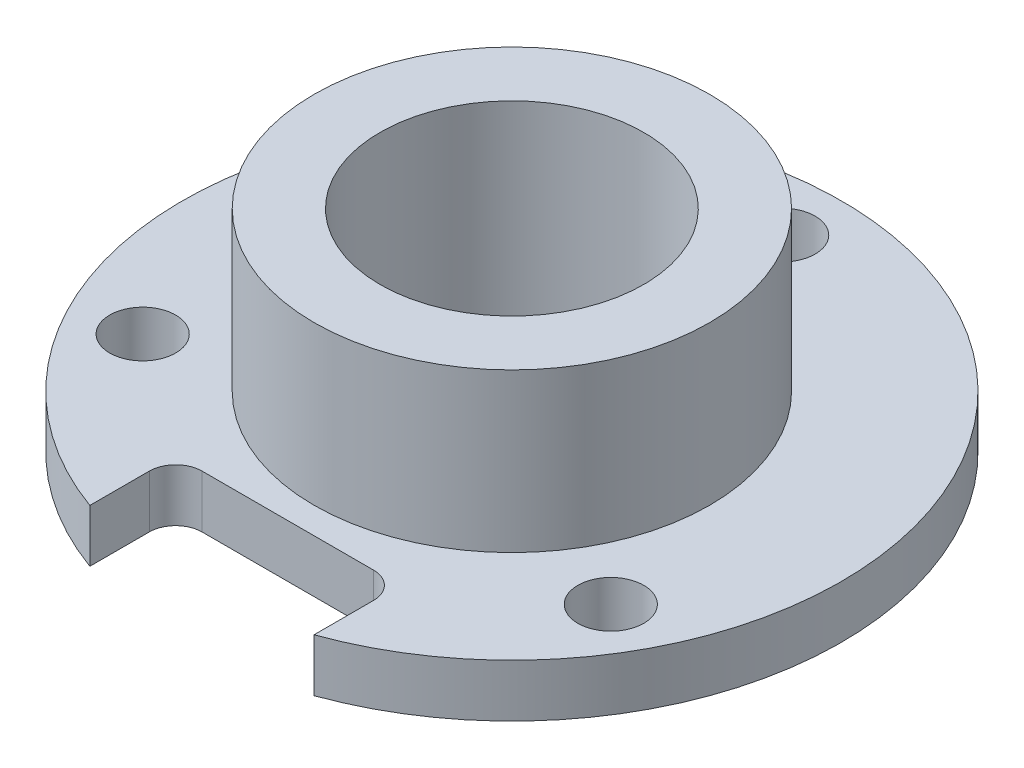
SolidWorks part; units mm, degrees
ref_plane "Front Plane" through (0, 0, 0) normal (0, 0, 1) x (1, 0, 0)
ref_plane "Top Plane" through (0, 0, 0) normal (0, 1, 0) x (1, 0, 0)
ref_plane "Right Plane" through (0, 0, 0) normal (1, 0, 0) x (0, 0, -1)
sketch "Sketch1" plane through (0, 0, 0) normal (0, 1, 0) x (1, 0, 0)
  circle A0 centre (0, 0) radius 7.5
  circle A1 centre (0, 0) radius 12.5
  circle A2 centre (0, 0) radius 5
  dimension "D1" = 15
  dimension "D2" = 25
  dimension "D3" = 10
extrude "Boss-Extrude1" add sketch "Sketch1" along normal blind 2 contours A1 A0 region at (-12.1464, 0, 0)
extrude "Boss-Extrude2" add sketch "Sketch1<3>" along normal blind 8 contours A0 region at (-7.2879, 0, 0)
sketch "Sketch1<3>" plane through (0, 0, 0) normal (0, 1, 0) x (1, 0, 0) same geometry as "Sketch1"
sketch "Sketch2" plane through (0, 2, 0) normal (0, 1, 0) x (1, 0, 0)
  line L1 (-4.25, -13.5) -> (4.25, -13.5)
  line L2 (-4.25, -13.5) -> (-4.25, -9.5)
  line L3 (-3.25, -8.5) -> (3.25, -8.5)
  line L4 (4.25, -13.5) -> (4.25, -9.5)
  line L5 (-4.25, -13.5) -> (4.25, -8.5) construction
  line L6 (-4.25, -8.5) -> (4.25, -13.5) construction
  arc A0 (3.25, -8.5) -> (4.25, -9.5) centre (3.25, -9.5) cw
  arc A1 (-4.25, -9.5) -> (-3.25, -8.5) centre (-3.25, -9.5) cw
  point P0 (0, -11)
  dimension "D4" = 1
  dimension "D1" = 8.5
  dimension "D2" = 8.5
  dimension "D3" = 5
extrude "Cut-Extrude1" cut sketch "Sketch2" against normal up to surface (2 mm away) contours L1 L4 A0 L3 A1 L2 up to face at (0, 0, 12.5)
sketch "Sketch3" plane through (0, 2, 0) normal (0, 1, 0) x (1, 0, 0)
  line L0 (0, 0) -> (0, 3.5924) construction
  circle A0 centre (0, 0) radius 10.25 construction
  arc A1 (4.25, -11.7553) -> (-4.25, -11.7553) centre (0, 0) ccw construction
  circle A2 centre (0, 10.25) radius 1.25
  circle A3 centre (8.8768, -5.125) radius 1.25
  circle A4 centre (-8.8768, -5.125) radius 1.25
  point P15 (0, 0)
  dimension "D2" = 2.5
  dimension "D1" = 2.25
  dimension "D3" = 3
extrude "Cut-Extrude2" cut sketch "Sketch3" against normal up to surface (2 mm away) up to face at (0, 0, 5)
equation "\"D1@Sketch3\"=1+1.25"
